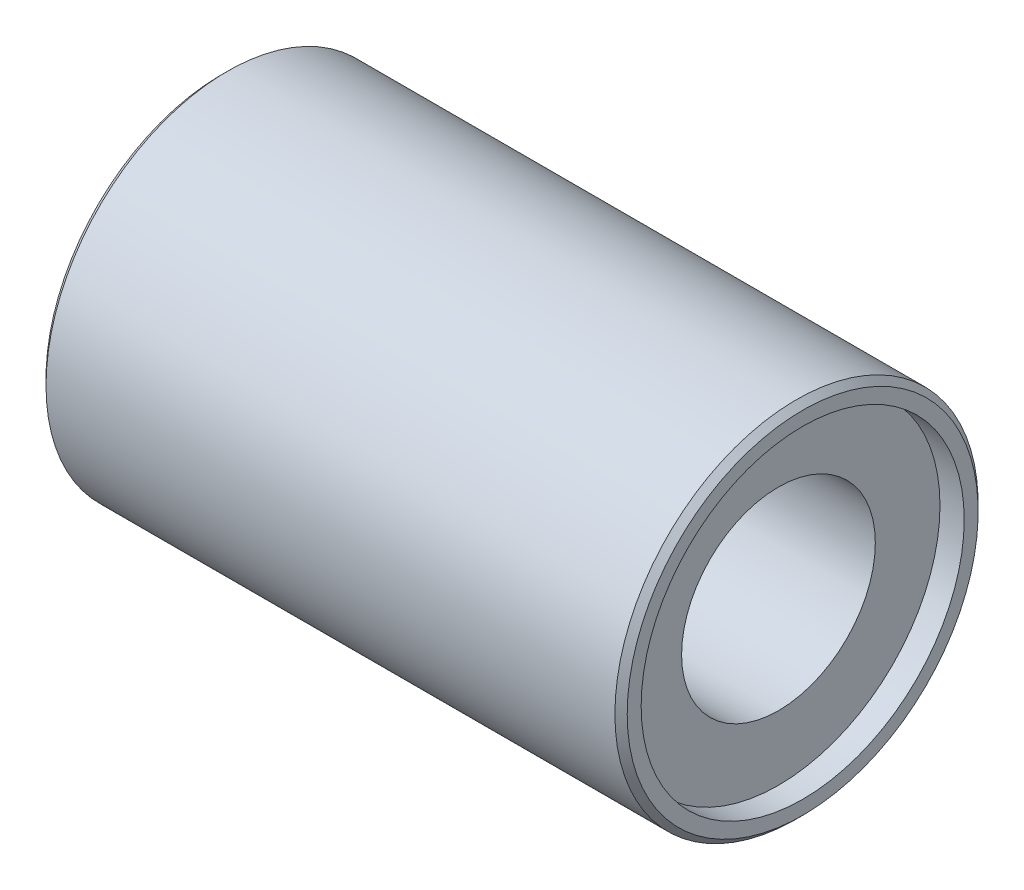
SolidWorks part; units mm, degrees
ref_plane "Front Plane" through (0, 0, 0) normal (0, 0, 1) x (1, 0, 0)
ref_plane "Top Plane" through (0, 0, 0) normal (0, 1, 0) x (1, 0, 0)
ref_plane "Right Plane" through (0, 0, 0) normal (1, 0, 0) x (0, 0, -1)
sketch "Sketch3" plane through (0, 0, 0) normal (0, 0, 1) x (1, 0, 0)
  line L0 (0, 0) -> (24, 0) construction
  line L1 (1, 4) -> (23, 4)
  line L2 (0, 7.5) -> (24, 7.5)
  line L3 (0, 6.67) -> (0, 7.5)
  line L4 (24, 6.67) -> (24, 7.5)
  line L5 (0, 6.67) -> (1, 6.67)
  line L6 (1, 4) -> (1, 6.67)
  line L7 (12, 7.5) -> (12, 0) construction
  line L8 (23, 4) -> (23, 6.67)
  line L9 (0, 4) -> (0, 7.5) construction
  line L10 (0, 4) -> (24, 4) construction
  line L11 (23, 6.67) -> (24, 6.67)
  line L12 (0, 6.67) -> (24, 6.67) construction
  line L13 (1, 4) -> (1, 7.5) construction
  dimension "D1" = 24
  dimension "D2" = 4
  dimension "D3" = 7.5
  dimension "D4" = 0.83
  dimension "D5" = 1
revolve "Revolve1" add sketch "Sketch3" angle 360 about L0
chamfer "Chamfer1" distance 0.254 angle 45 2 edges at (0, 0, 7.5) (24, 0, 7.5)
